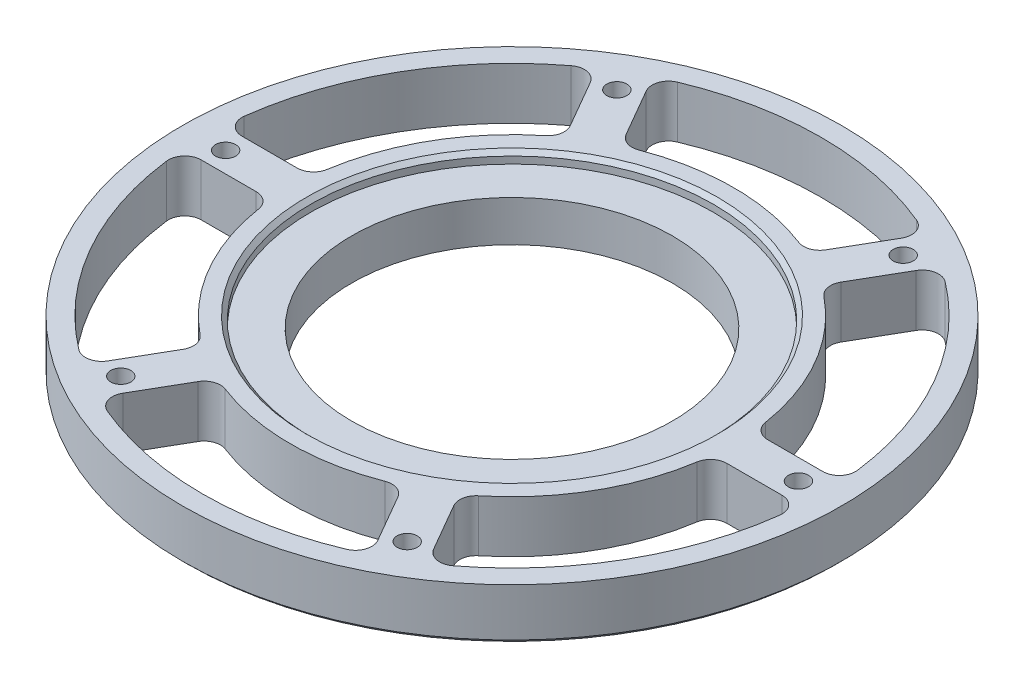
SolidWorks part; units mm, degrees
material "6061-T6 (SS)"
ref_plane "Front Plane" through (0, 0, 0) normal (0, 0, 1) x (1, 0, 0)
ref_plane "Top Plane" through (0, 0, 0) normal (0, 1, 0) x (1, 0, 0)
ref_plane "Right Plane" through (0, 0, 0) normal (1, 0, 0) x (0, 0, -1)
sketch "Sketch2" plane through (0, 0, 0) normal (1, 0, 0) x (0, 0, -1)
  line L0 (-39.2125, 0) -> (-80.55, 0)
  line L1 (-80.55, 0) -> (-80.55, 12.7)
  line L2 (-80.55, 12.7) -> (-49.2125, 12.7)
  line L3 (-49.2125, 12.7) -> (-49.2125, 10)
  line L4 (-49.2125, 10) -> (-39.2125, 10)
  line L5 (-39.2125, 10) -> (-39.2125, 0)
  dimension "D1" = 80.55
  dimension "D2" = 12.7
  dimension "D4" = 49.2125
  dimension "D5" = 10
  dimension "D3" = 10
ref_axis "Axis1" through (0, -0.635, 0) along (0, 1, 0)
revolve "Revolve1" add sketch "Sketch2" angle 360 about axis through (0, -0.635, 0) along (0, 1, 0)
hole_wizard "#10 (0.1935) Diameter Hole1" positions "Sketch6" profile "Sketch7" hole size "#10" standard "ANSI Inch" end condition through all
sketch "Sketch6" plane through (0, 12.7, 0) normal (0, 1, 0) x (1, 0, 0)
  line L0 (0, 0) -> (-69.8201, 120.932) construction
  line L2 (0, 0) -> (0, 109.0908) construction
  point P0 (-35, 60.6218)
  dimension "D1" = 30
  dimension "D2" = 70
sketch "Sketch7" plane through (-35, 12.7, -60.6218) normal (1, 0, 0) x (0, 0, 1)
  line L0 (0, 0) -> (0, 12.7)
  line L1 (0, 12.7) -> (2.4574, 12.7)
  line L2 (2.4574, 12.7) -> (2.4574, 0)
  line L5 (2.4574, 0) -> (0, 0)
  line L11 (0, -6.35) -> (0, 107.95) construction
  dimension "Thru Hole Dia." = 4.9149
  dimension "Thru Hole Depth" = 12.7
pattern_circular "CirPattern3" count 6 over 360 about axis through (0, -0.635, 0) along (0, 1, 0) of "#10 (0.1935) Diameter Hole1"
sketch "Sketch8" plane through (0, 12.7, 0) normal (0, 1, 0) x (1, 0, 0)
  line L0 (-33.3621, 67.7848) -> (-22.6606, 49.2493)
  line L1 (33.3621, 67.7848) -> (22.6606, 49.2493)
  line L2 (0, 0) -> (-35, 60.6218) construction
  line L4 (0, 0) -> (0, 93.9995) construction
  arc A0 (-22.6606, 49.2493) -> (22.6606, 49.2493) centre (0, 0) cw
  arc A1 (-33.3621, 67.7848) -> (33.3621, 67.7848) centre (0, 0) cw
  circle A2 centre (0, 0) radius 49.2125 construction
  circle A3 centre (0, 0) radius 80.55 construction
  dimension "D1" = 5
  dimension "D2" = 5
  dimension "D3" = 5
extrude "Cut-Extrude1" cut sketch "Sketch8" against normal through all
fillet "Fillet1" radius 4 4 edges at (33.3621, 6.35, -67.7848) (22.6606, 6.35, -49.2493) (-33.3621, 6.35, -67.7848) (-22.6606, 6.35, -49.2493)
pattern_circular "CirPattern4" count 6 over 360 about axis through (0, -0.635, 0) along (0, 1, 0) of "Cut-Extrude1", "Fillet1"
chamfer "Chamfer1" distance 1 angle 45 1 edges at (0, 12.7, -49.2125)
chamfer "Chamfer2" distance 1 angle 45 1 edges at (0, 0, -80.55)
equation "\"TubeDiameter\" = 6.500in"
equation "\"D1@Sketch2\"=(\"TubeDiameter\"-4)/2"
